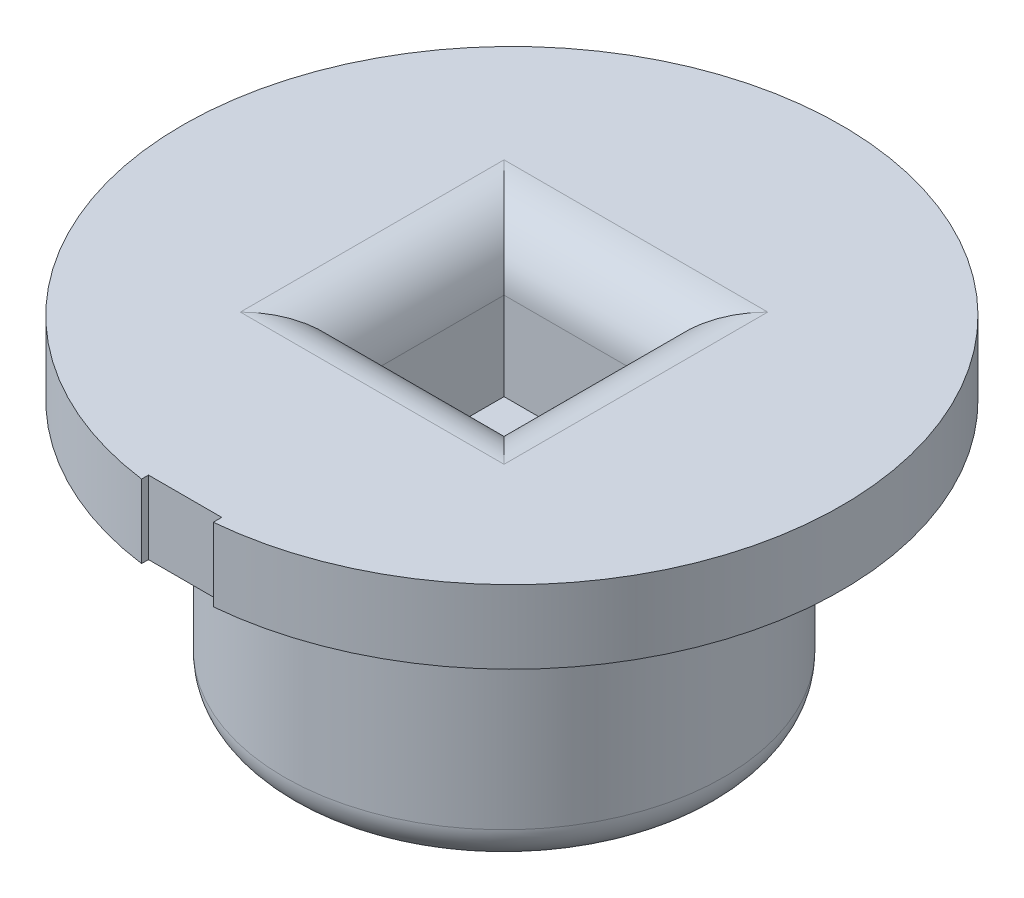
SolidWorks part; units mm, degrees
ref_plane "前视基准面" through (0, 0, 0) normal (0, 0, 1) x (1, 0, 0)
ref_plane "上视基准面" through (0, 0, 0) normal (0, 1, 0) x (1, 0, 0)
ref_plane "右视基准面" through (0, 0, 0) normal (1, 0, 0) x (0, 0, -1)
sketch "草图1" plane through (0, 0, 0) normal (0, 1, 0) x (1, 0, 0)
  circle A0 centre (0, 0) radius 3
  dimension "D1" = 6
extrude "凸台-拉伸1" add sketch "草图1" along normal blind 3.5 contours A0
sketch "草图2" plane through (0, 3.5, 0) normal (0, 1, 0) x (1, 0, 0)
  circle A0 centre (0.0949, 0.012) radius 4.5
  dimension "D1" = 9
extrude "凸台-拉伸2" add sketch "草图2" along normal blind 1
sketch "草图4" plane through (0, 4.5, 0) normal (0, 1, 0) x (1, 0, 0)
  line L1 (1, -1) -> (-1, -1)
  line L2 (1, -1) -> (1, 1)
  line L3 (1, 1) -> (-1, 1)
  line L4 (-1, -1) -> (-1, 1)
  line L5 (1, -1) -> (-1, 1) construction
  line L6 (1, 1) -> (-1, -1) construction
  circle A0 centre (0, 0) radius 3 construction
  point P0 (0, 0)
  dimension "D1" = 2
  dimension "D2" = 2
extrude "切除-拉伸1" cut sketch "草图4" against normal blind 2
fillet "圆角1" radius 0.5 1 edges at (0, 0, 3)
fillet "圆角2" radius 0.8 4 edges at (0, 4.5, 1) (-1, 4.5, 0) (0, 4.5, -1) (1, 4.5, 0)
sketch "草图5" plane through (0, 3.5, 0) normal (0, -1, 0) x (1, 0, 0)
  line L1 (-0.5, 5.0111) -> (0.5, 5.0111)
  line L2 (-0.5, 5.0111) -> (-0.5, 4.3544)
  line L3 (-0.5, 4.3544) -> (0.5, 4.3544)
  line L4 (0.5, 5.0111) -> (0.5, 4.3544)
  point P4 (0, 4.3544)
  dimension "D1" = 0.6567
  dimension "D2" = 1
extrude "切除-拉伸2" cut sketch "草图5" against normal blind 1
